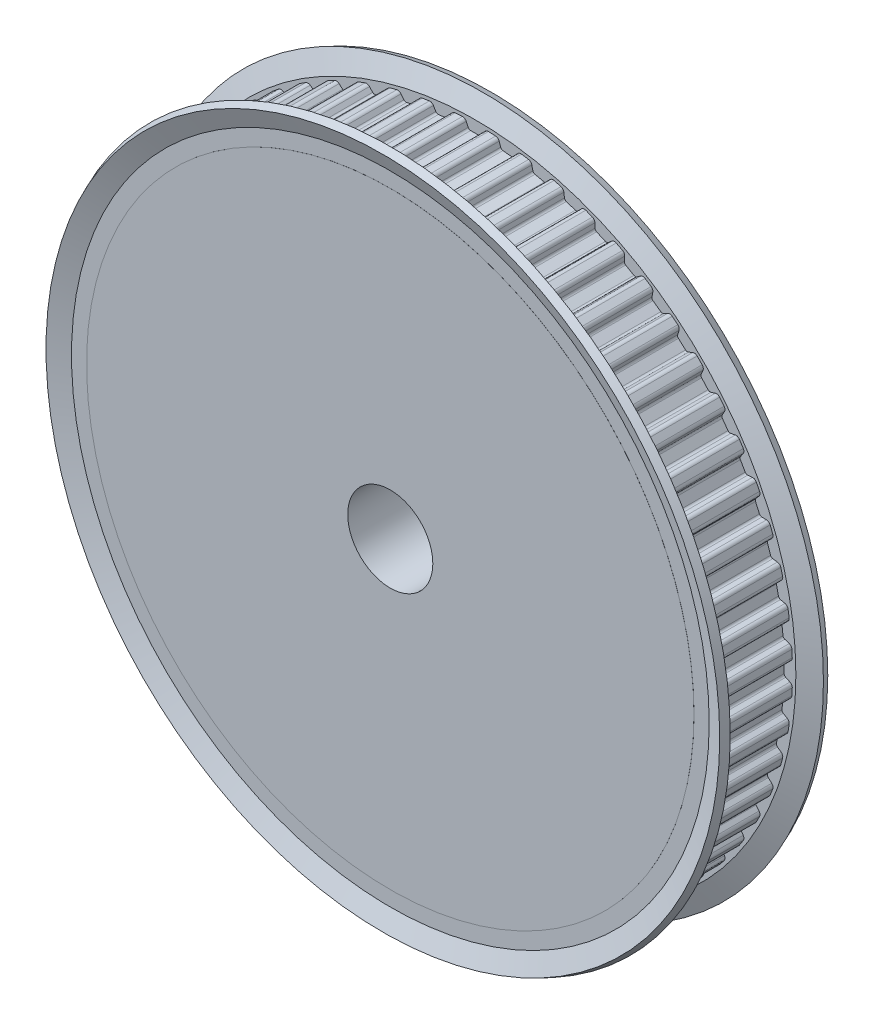
SolidWorks part; units mm, degrees
ref_plane "Plano frontal" through (0, 0, 0) normal (0, 0, 1) x (1, 0, 0)
ref_plane "Plano superior" through (0, 0, 0) normal (0, 1, 0) x (1, 0, 0)
ref_plane "Plano direito" through (0, 0, 0) normal (1, 0, 0) x (0, 0, -1)
ref_axis "Eixo1" through (0, 0, 55) along (0, 0, -1)
sketch "SketchRevolveGearBelt01" plane through (0, 0, 0) normal (1, 0, 0) x (0, 0, -1)
  line L0 (0, 0) -> (25.4, 0) construction
  line L1 (6.96, 0) -> (6.96, 45.325)
  line L2 (6.96, 45.325) -> (6.95, 45.325)
  line L3 (6.95, 45.325) -> (6.95, 47.5863)
  line L4 (6.95, 47.5863) -> (8.0633, 50.2741)
  line L5 (8.0633, 50.2741) -> (6.9547, 50.7333)
  line L6 (6.9547, 50.7333) -> (5.75, 47.825)
  line L7 (5.75, 47.825) -> (5.75, 47.325)
  line L8 (5.75, 47.325) -> (-5.75, 47.325)
  line L9 (-5.75, 47.325) -> (-5.75, 47.825)
  line L10 (-5.75, 47.825) -> (-6.9547, 50.7333)
  line L11 (-6.9547, 50.7333) -> (-8.0633, 50.2741)
  line L12 (-8.0633, 50.2741) -> (-6.95, 47.5863)
  line L13 (-6.95, 47.5863) -> (-6.95, 45.325)
  line L14 (-6.95, 45.325) -> (-6.96, 45.325)
  line L15 (-6.96, 45.325) -> (-6.96, 0)
  line L16 (-6.96, 0) -> (6.96, 0)
  dimension "GearBeltFlange1OutsideLength" = 2.2613
  dimension "GearBeltFlange1X" = 1.1133
  dimension "GearBeltFlange1Y" = 2.6878
  dimension "GearBeltFlangeThickness" = 1.2
  dimension "GearBeltFlangeInside" = 0.5
  dimension "GearBeltOutsideDiameter" = 47.325
  dimension "GearBeltFlange2X" = 1.1133
revolve "GearBelt01" add sketch "SketchRevolveGearBelt01" angle 360 about L0
sketch "SketchToothGearBelt01" plane through (0, 0, 0) normal (0, 0, 1) x (1, 0, 0)
  line L0 (-1.3748, 46.9392) -> (-1.0795, 46.306)
  line L1 (-0.717, 46.075) -> (0.717, 46.075)
  line L2 (1.0795, 46.306) -> (1.3748, 46.9392)
  line L3 (1.9432, 47.2851) -> (0, 49.8251)
  line L4 (0, 49.8251) -> (-1.9432, 47.2851)
  arc A0 (-1.9432, 47.2851) -> (-1.3748, 46.9392) centre (-1.9186, 46.6856) cw
  arc A1 (-1.0795, 46.306) -> (-0.717, 46.075) centre (-0.717, 46.475) ccw
  arc A2 (0.717, 46.075) -> (1.0795, 46.306) centre (0.717, 46.475) ccw
  arc A3 (1.3748, 46.9392) -> (1.9432, 47.2851) centre (1.9186, 46.6856) cw
  dimension "GearBeltToothR1" = 1.2
  dimension "GearBeltToothR2" = 0.8
  dimension "GearBeltToothX1" = 0.2953
  dimension "GearBeltToothY1" = 0.6332
  dimension "GearBeltToothX2" = 0.2953
  dimension "GearBeltToothY2" = 0.6332
  dimension "GearBeltToothCapX1" = 1.9432
  dimension "GearBeltToothCapY1" = 2.54
  dimension "GearBeltToothCapX2" = 1.9432
  dimension "GearBeltToothCapY2" = 2.54
extrude "ToothExtrudeCutGearBelt01" cut sketch "SketchToothGearBelt01" against normal blind 5.75 and the other way blind 5.75
ref_axis "Eixo2" through (55.8066, 0, 0) along (-1, 0, 0)
ref_plane "Plano1" through (0, 0, 0) normal (0, 0, -1) x (1, 0, 0)
pattern_circular "PatternGearBelt01" count 60 every 6 about axis through (0, 0, 55) along (0, 0, -1) of "ToothExtrudeCutGearBelt01"
sketch "BoreRevolveSketch" plane through (0, 0, 0) normal (1, 0, 0) x (0, 0, -1)
  line L0 (0, 0) -> (25.4, 0) construction
  line L1 (-6.96, 0) -> (6.96, 0)
  line L2 (6.96, 0) -> (6.96, 6.35)
  line L3 (6.96, 6.35) -> (-6.96, 6.35)
  line L4 (-6.96, 6.35) -> (-6.96, 0)
  dimension "TaperSide1" = 6.35
  dimension "TaperSide2" = 6.35
revolve "BoreRevolveCut" cut sketch "BoreRevolveSketch" angle 360 about L0
sketch "AuxiliarySketchGearBelt01" plane through (0, 0, 0) normal (0, 0, 1) x (1, 0, 0)
  circle A0 centre (0, 0) radius 47.825 construction
  dimension "PitchDiameter" = 95.65
